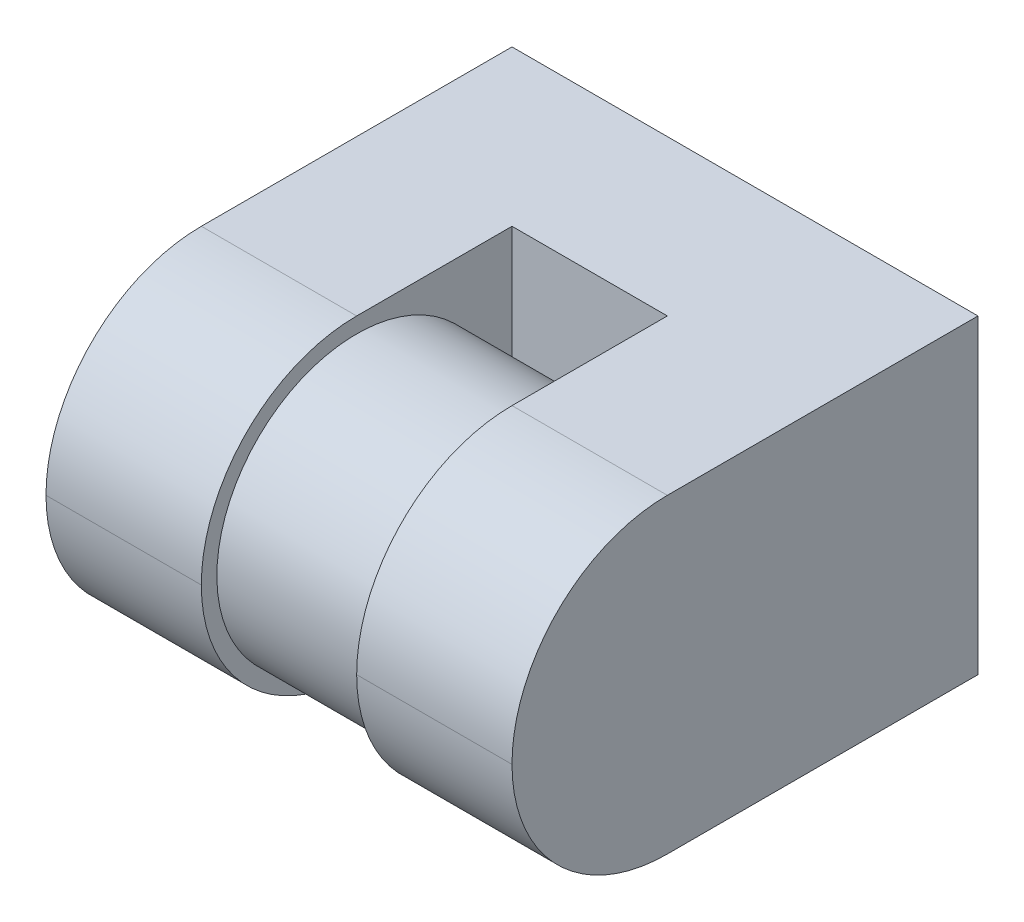
SolidWorks part; units mm, degrees
ref_plane "Płaszczyzna przednia" through (0, 0, 0) normal (0, 0, 1) x (1, 0, 0)
ref_plane "Płaszczyzna górna" through (0, 0, 0) normal (0, 1, 0) x (1, 0, 0)
ref_plane "Płaszczyzna prawa" through (0, 0, 0) normal (1, 0, 0) x (0, 0, -1)
sketch "Szkic1" plane through (0, 0, 0) normal (0, 0, 1) x (1, 0, 0)
  line L1 (0, 0) -> (30, 0)
  line L2 (0, 0) -> (0, 20)
  line L3 (0, 20) -> (30, 20)
  line L4 (30, 0) -> (30, 20)
  circle A0 centre (15, 10) radius 2.6
  point P7 (0, 0)
  dimension "D3" = 5.2
  dimension "D1" = 30
  dimension "D2" = 20
  dimension "D4" = 15
  dimension "D5" = 10
extrude "Dodanie-wyciągnięcie1" add sketch "Szkic1" along normal blind 10
sketch "Szkic2" plane through (0, 0, 10) normal (0, 0, 1) x (1, 0, 0)
  line L0 (0, 0) -> (30, 0) construction
  line L1 (0, 20) -> (10, 20)
  line L2 (0, 20) -> (0, 0)
  line L3 (0, 0) -> (10, 0)
  line L4 (10, 20) -> (10, 0)
  line L6 (20, 0) -> (30, 0)
  line L7 (20, 0) -> (20, 20)
  line L8 (20, 20) -> (30, 20)
  line L9 (30, 0) -> (30, 20)
  dimension "D1" = 10
  dimension "D2" = 10
extrude "Dodanie-wyciągnięcie2" add sketch "Szkic2" along normal blind 20
sketch "Szkic3" plane through (10, 0, 0) normal (1, 0, 0) x (0, 0, -1)
  line L0 (-30, 0) -> (-30, 20) construction
  line L1 (-30, 20) -> (-10, 20) construction
  circle A0 centre (-20, 10) radius 9
  dimension "D3" = 18
  dimension "D1" = 10
  dimension "D2" = 10
extrude "Dodanie-wyciągnięcie3" add sketch "Szkic3" along normal blind 10
fillet "Zaokrąglenie1" radius 10 4 edges at (25, 0, 30) (5, 0, 30) (25, 20, 30) (5, 20, 30)
